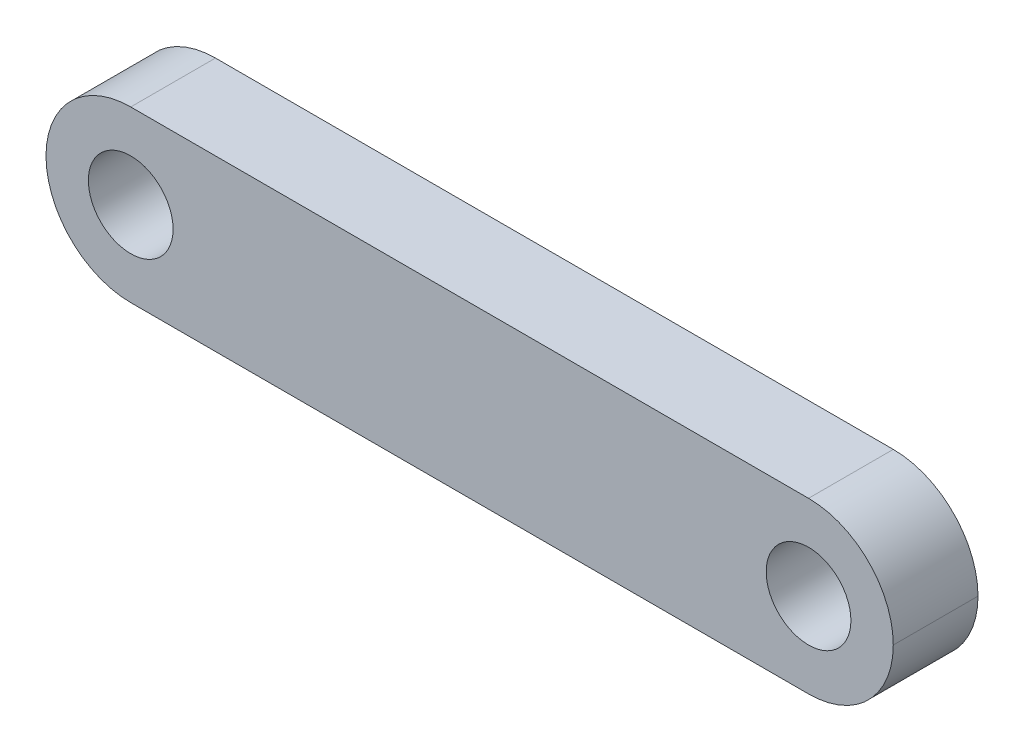
SolidWorks part; units mm, degrees
ref_plane "Front Plane" through (0, 0, 0) normal (0, 0, 1) x (1, 0, 0)
ref_plane "Top Plane" through (0, 0, 0) normal (0, 1, 0) x (1, 0, 0)
ref_plane "Right Plane" through (0, 0, 0) normal (1, 0, 0) x (0, 0, -1)
sketch "Sketch1" plane through (0, 0, 0) normal (0, 0, 1) x (1, 0, 0)
  line L1 (0, 0) -> (100, 0)
  line L2 (0, 0) -> (0, 20)
  line L3 (0, 20) -> (100, 20)
  line L4 (100, 0) -> (100, 20)
  dimension "D1" = 20
  dimension "D2" = 100
extrude "Boss-Extrude1" add sketch "Sketch1" along normal blind 10
fillet "Fillet1" radius 10 4 edges at (100, 20, 5) (100, 0, 5) (0, 0, 5) (0, 20, 5)
sketch "Sketch5" plane through (0, 0, 10) normal (0, 0, 1) x (1, 0, 0)
  circle A0 centre (10, 10) radius 5
  circle A1 centre (90, 10) radius 5
  arc A3 (10, 20) -> (0, 10) centre (10, 10) ccw construction
  arc A4 (100, 10) -> (90, 20) centre (90, 10) ccw construction
  point P6 (0, 0)
  point P7 (0, 0)
  dimension "D2" = 10
  dimension "D3" = 10
extrude "Cut-Extrude1" cut sketch "Sketch5" against normal through all
